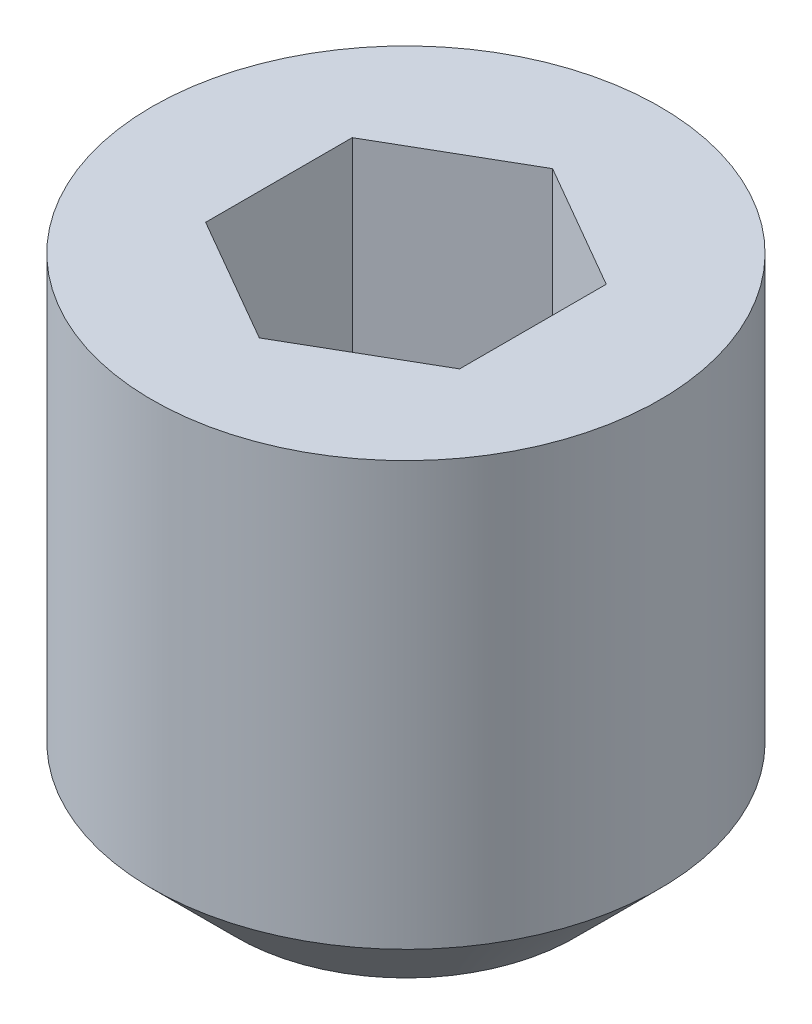
SolidWorks part; units mm, degrees
ref_plane "Front Plane" through (0, 0, 0) normal (0, 0, 1) x (1, 0, 0)
ref_plane "Top Plane" through (0, 0, 0) normal (0, 1, 0) x (1, 0, 0)
ref_plane "Right Plane" through (0, 0, 0) normal (1, 0, 0) x (0, 0, -1)
ref_axis "Axis_X" through (-88.99, 0, 0) along (1, 0, 0)
ref_axis "Axis_Y" through (0, 56.5, 0) along (0, -1, 0)
ref_axis "Axis_Z" through (0, 0, -88.99) along (0, 0, 1)
sketch "Sketch1" plane through (0, 0, 0) normal (0, 0, 1) x (1, 0, 0)
  line L0 (0, 3) -> (0, 0) construction
  line L2 (0, 3) -> (1.5, 3)
  line L3 (0, 3) -> (0, 0)
  line L4 (0, 0) -> (1.5, 0)
  line L5 (1.5, 3) -> (1.5, 0)
  dimension "TPC" = 3
  dimension "SS_L" = 3
revolve "Revolve1" add sketch "Sketch1" angle 360 about L0
cosmetic thread "Cosmetic Thread1" parameters "SS_D1_s"=2.459
sketch "Sketch2" plane through (0, 0, 0) normal (0, 0, 1) x (1, 0, 0)
  line L0 (0, 3) -> (0, 1.367) construction
  line L1 (0, 3) -> (0.75, 3)
  line L3 (0.75, 3) -> (0.75, 1.8)
  line L4 (0.75, 1.8) -> (0, 1.367)
  line L5 (0, 1.367) -> (0, 3)
  line L6 (1.5, 3) -> (-1.5, 3) construction
  dimension "D1" = 60
  dimension "SS_B" = 1.5
  dimension "SS_C" = 1.2
revolve "Cut-Revolve1" cut sketch "Sketch2" angle 360 about L0
sketch "Sketch3" plane through (0, 3, 0) normal (0, 1, 0) x (1, 0, 0)
  line L1 (0, 0.866) -> (-0.75, 0.433)
  line L2 (-0.75, 0.433) -> (-0.75, -0.433)
  line L3 (-0.75, -0.433) -> (0, -0.866)
  line L4 (0, -0.866) -> (0.75, -0.433)
  line L5 (0.75, -0.433) -> (0.75, 0.433)
  line L6 (0.75, 0.433) -> (0, 0.866)
  circle A0 centre (0, 0) radius 0.75 construction
  circle A1 centre (0, 0) radius 0.75 construction
extrude "Cut-Extrude1" cut sketch "Sketch3" against normal blind 1.2
sketch "Sketch4" plane through (0, 0, 0) normal (0, 0, 1) x (1, 0, 0)
  line L0 (0, 3) -> (0, 0) construction
  line L1 (1.5, 3) -> (1.5, 0) construction
  line L2 (-1.5, 0) -> (1.5, 0) construction
  line L3 (1.5, 0.5) -> (1.5, 0)
  line L4 (1.5, 0) -> (1, 0)
  line L5 (1, 0) -> (1.5, 0.5)
  dimension "D1" = 45
  dimension "SS_D_s" = 2
revolve "Cut-Revolve2" cut sketch "Sketch4" angle 360 about L0
